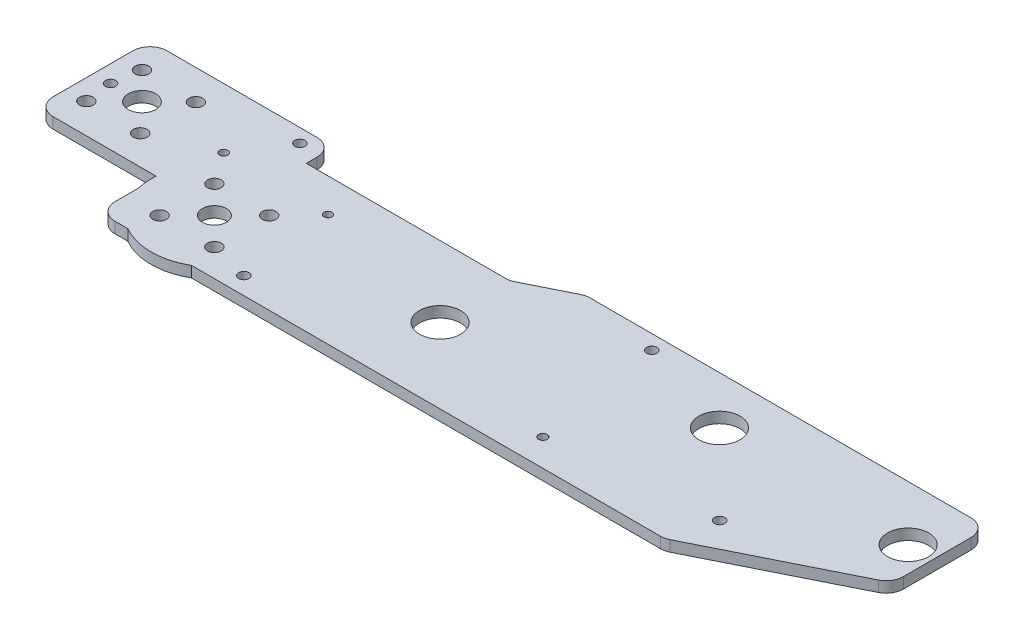
SolidWorks part; units mm, degrees
ref_plane "Front" through (0, 0, 0) normal (0, 0, 1) x (1, 0, 0)
ref_plane "Top" through (0, 0, 0) normal (0, 1, 0) x (1, 0, 0)
ref_plane "Right" through (0, 0, 0) normal (1, 0, 0) x (0, 0, -1)
sketch "Sketch1" plane through (0, 0, 0) normal (0, 1, 0) x (1, 0, 0)
  line L1 (0, 0) -> (210, 0)
  line L2 (0, 0) -> (0, -50)
  line L3 (0, -50) -> (210, -50)
  line L4 (210, 0) -> (210, -50)
  circle A7 centre (3.4895, -16.7877) radius 1.2117
  circle A8 centre (34.3726, -17.194) radius 1.1656
  circle A9 centre (37.5207, -44.9212) radius 1.5
  circle A10 centre (122, -42.0581) radius 1.25
  circle A12 centre (168.9752, -37.4032) radius 1.5173
  circle A13 centre (78.0103, -28.1) radius 3.4
  dimension "D1" = 210
  dimension "D2" = 50
extrude "Boss-Extrude1" add sketch "Sketch1" along normal blind 3.175
sketch "Sketch2" plane through (0, 3.175, 0) normal (0, 1, 0) x (1, 0, 0)
  line L0 (210, 0) -> (0, 0) construction
  line L1 (0, 0) -> (0, -50) construction
  circle A0 centre (10, -26) radius 2
  circle A1 centre (10, -42) radius 2
  circle A2 centre (26, -26) radius 2
  circle A3 centre (26, -42) radius 2
  dimension "D1" = 16
  dimension "D2" = 16
  dimension "D3" = 16
  dimension "D4" = 26
  dimension "D5" = 10
  dimension "D6" = 10
  dimension "D7" = 26
  dimension "D8" = 16
extrude "Cut-Extrude1" cut sketch "Sketch2" against normal blind 10
sketch "Sketch3" plane through (0, 3.175, 0) normal (0, 1, 0) x (1, 0, 0)
  line L0 (210, 0) -> (0, 0) construction
  line L1 (210, 0) -> (0, 0) construction
  circle A0 centre (78.0103, -28.1) radius 6
  circle A1 centre (145.5313, -14) radius 6
  circle A2 centre (18, -34) radius 0.587
  circle A3 centre (26, -26) radius 2 construction
  circle A4 centre (202.6463, -16) radius 6
  dimension "D1" = 28.1
  dimension "D3" = 16
  dimension "D4" = 14
  dimension "D7" = 125.222
  dimension "D2" = 60.2996
  dimension "D5" = 8
  dimension "D6" = 8
  dimension "D8" = 57.15
extrude "Cut-Extrude2" cut sketch "Sketch3" against normal blind 57.15
sketch "Sketch4" [suppressed] plane through (0, 3.175, 0) normal (0, 1, 0) x (1, 0, 0)
  line L0 (3.4895, -16.7877) -> (18, -34)
  line L1 (3.4895, -20.6627) -> (5.9498, -23.5811)
  line L2 (18, -34) -> (34.3726, -17.194)
  line L3 (34.3726, -17.194) -> (75.8499, -28.1)
  line L4 (75.8499, -28.1) -> (37.5207, -44.9212)
  line L5 (7.3432, -17.194) -> (9.8664, -20.303)
  circle A0 centre (18, -34) radius 15.9299
  circle A1 centre (3.4895, -16.7877) radius 3.8751
  circle A2 centre (34.3726, -17.194) radius 3.7227
  circle A3 centre (37.5207, -44.9212) radius 3.8676
  circle A4 centre (75.8499, -28.1) radius 12.797
  circle A5 centre (112.3021, -4.7393) radius 5.1588
  circle A6 centre (118.879, -40.0177) radius 4.9035
  circle A7 centre (140.772, -16) radius 12.6375
  circle A8 centre (168.9752, -37.4032) radius 4.2066
  circle A9 centre (197.922, -16) radius 12.8
sketch "Sketch5" [suppressed] plane through (0, 3.175, 0) normal (0, 1, 0) x (1, 0, 0)
  line L0 (210, 0) -> (0, 0) construction
  line L2 (-0.6266, -16.7877) -> (37.5207, -16.7877)
  line L3 (-0.6266, -16.7877) -> (-0.6266, -44.9212)
  line L4 (-0.6266, -44.9212) -> (37.5207, -44.9212)
  line L5 (37.5207, -16.7877) -> (37.5207, -44.9212)
  line L6 (75.8499, -15.182) -> (37.5207, -15.182)
  line L7 (75.8499, -15.182) -> (75.8499, -44.9212)
  line L8 (75.8499, -44.9212) -> (37.5207, -44.9212)
  line L9 (37.5207, -15.182) -> (37.5207, -44.9212)
  line L10 (112.3021, -4.7393) -> (75.8499, -4.7393)
  line L11 (112.3021, -4.7393) -> (112.3021, -44.9212)
  line L12 (112.3021, -44.9212) -> (75.8499, -44.9212)
  line L13 (75.8499, -4.7393) -> (75.8499, -44.9212)
  line L14 (112.3021, -4.7393) -> (102.3945, -4.7393)
  line L16 (112.3021, -4.7393) -> (112.3021, 0)
  line L17 (112.3021, 0) -> (102.3945, 0)
  line L18 (102.3945, -4.7393) -> (102.3945, 0)
  line L19 (210, -50) -> (210, 0) construction
  line L20 (112.3021, -4.7393) -> (123.1553, -4.7393)
  line L21 (112.3021, -4.7393) -> (112.3021, 0)
  line L22 (112.3021, 0) -> (123.1553, 0)
  line L23 (123.1553, -4.7393) -> (123.1553, 0)
  line L24 (112.3021, -4.7393) -> (140.772, -4.7393)
  line L25 (112.3021, -4.7393) -> (112.3021, -40.0177)
  line L26 (112.3021, -40.0177) -> (140.772, -40.0177)
  line L27 (140.772, -4.7393) -> (140.772, -40.0177)
  line L28 (140.772, -16) -> (168.9752, -16)
  line L29 (140.772, -16) -> (140.772, -40.0177)
  line L30 (140.772, -40.0177) -> (168.9752, -40.0177)
  line L31 (168.9752, -16) -> (168.9752, -40.0177)
  line L32 (168.9752, -4.7393) -> (210, -4.7393)
  line L33 (168.9752, -4.7393) -> (168.9752, -40.0177)
  line L34 (168.9752, -40.0177) -> (210, -40.0177)
  line L35 (210, -4.7393) -> (210, -40.0177)
  line L36 (0, -50) -> (210, -50) construction
  line L37 (160.7629, -40.0177) -> (177.2091, -40.0177)
  line L38 (160.7629, -40.0177) -> (160.7629, -44.9212)
  line L39 (160.7629, -44.9212) -> (177.2091, -44.9212)
  line L40 (177.2091, -40.0177) -> (177.2091, -44.9212)
  line L41 (112.3021, -40.0177) -> (126.3591, -40.0177)
  line L42 (112.3021, -40.0177) -> (112.3021, -47.7828)
  line L43 (112.3021, -47.7828) -> (126.3591, -47.7828)
  line L44 (126.3591, -40.0177) -> (126.3591, -47.7828)
  line L45 (30.5963, -44.9212) -> (44.6115, -44.9212)
  line L46 (30.5963, -44.9212) -> (30.5963, -50)
  line L47 (30.5963, -50) -> (44.6115, -50)
  line L48 (44.6115, -44.9212) -> (44.6115, -50)
  line L50 (-0.6266, -44.9212) -> (30.5963, -44.9212)
  line L51 (-0.6266, -44.9212) -> (-0.6266, -50)
  line L52 (-0.6266, -50) -> (30.5963, -50)
  line L53 (30.5963, -44.9212) -> (30.5963, -50)
  circle A0 centre (3.4895, -16.7877) radius 4.1161
  circle A1 centre (34.3726, -17.194) radius 3.8132
  circle A2 centre (75.8499, -28.1) radius 12.918
  circle A3 centre (112.3021, -4.7393) radius 5.2663
  circle A4 centre (140.772, -16) radius 13.0245
  circle A5 centre (197.922, -16) radius 12.3805
  circle A6 centre (168.9752, -37.4032) radius 4.7643
  circle A7 centre (118.879, -40.0177) radius 5.279
  circle A8 centre (37.5207, -44.9212) radius 4.2049
  line M12 (0, 0) -> (0, -50)
  line M13 (0, -50) -> (210, -50)
  line M14 (210, -50) -> (210, 0)
  line M15 (210, 0) -> (0, 0)
extrude "Cut-Extrude5" [suppressed] cut sketch "Sketch5" against normal blind 11.52 contours A5 L32 L23 L24 A4 L28 L33 M14 M15 | A1 L6 L13 L10 L18 A0 L2 M15 M12 | L8 L48 L34 L40 L39 L38 L30 L26 L44 L43 L42 L12 M13 M14
fillet "Fillet1" [suppressed] radius 5
sketch "Sketch10" plane through (0, 3.175, 0) normal (0, 1, 0) x (1, 0, 0)
  line L0 (210, -27.8594) -> (165.5029, -50)
  line L1 (210, -50) -> (210, 0) construction
  line L2 (0, -50) -> (210, -50) construction
  line L3 (165.5029, -50) -> (210, -50)
  line L4 (210, -50) -> (210, -27.8594)
  line L5 (92.5326, 0) -> (77.6548, -7.4028)
  line L6 (210, 0) -> (0, 0) construction
  line L7 (77.6548, -7.4028) -> (0, -7.4028)
  line L8 (0, 0) -> (0, -50) construction
  line L9 (0, -7.4028) -> (0, 0)
  line L10 (0, 0) -> (92.5326, 0)
extrude "Cut-Extrude7" cut sketch "Sketch10" against normal blind 10
fillet "Fillet3" radius 5 5 edges at (77.6548, 1.5875, 7.4028) (92.5326, 1.5875, 0) (210, 1.5875, 0) (210, 1.5875, 27.8594) (165.5029, 1.5875, 50)
sketch "Sketch11" plane through (0, 3.175, 0) normal (0, 1, 0) x (1, 0, 0)
  circle A0 centre (18, -34) radius 18.5
  circle A1 centre (10, -26) radius 2
  circle A2 centre (10, -42) radius 2
  circle A3 centre (26, -26) radius 2
  circle A4 centre (26, -42) radius 2
extrude "Boss-Extrude4" add sketch "Sketch11" against normal blind 3.175
sketch "Sketch16" plane through (0, 0, 7.4028) normal (0, 0, -1) x (-1, 0, 0)
  line L0 (0, 3.175) -> (-76.4796, 3.175) construction
  line L1 (0, 0) -> (-18.2576, 0)
  line L2 (0, 0) -> (0, 3.175)
  line L3 (0, 3.175) -> (-18.2576, 3.175)
  line L4 (-18.2576, 0) -> (-18.2576, 3.175)
extrude "Boss-Extrude7" add sketch "Sketch16" along normal blind 8.128
sketch "Sketch17" plane through (0, 0, 0) normal (-1, 0, 0) x (0, 0, 1)
  line L0 (-0.7252, 3.175) -> (29.728, 3.175) construction
  line L1 (-0.7252, 0) -> (32.5748, 0)
  line L2 (-0.7252, 0) -> (-0.7252, 3.175)
  line L3 (-0.7252, 3.175) -> (32.5748, 3.175)
  line L4 (32.5748, 0) -> (32.5748, 3.175)
  dimension "D1" = 33.3
extrude "Boss-Extrude8" add sketch "Sketch17" along normal blind 35.56
sketch "Sketch18" plane through (0, 3.175, 0) normal (0, 1, 0) x (1, 0, 0)
  line L0 (-35.56, 0.7252) -> (18.2576, 0.7252) construction
  circle A0 centre (-21.4859, -15.9248) radius 11.315
  circle A1 centre (-29.612, -23.7985) radius 2
  circle A2 centre (-29.3597, -7.7987) radius 2
  circle A3 centre (-13.3598, -8.0511) radius 2
  circle A4 centre (-13.6122, -24.0509) radius 2
  circle A5 centre (-21.4859, -15.9248) radius 4
  point P15 (-21.4859, -15.9248)
  dimension "D1" = 22.63
  dimension "D3" = 4
  dimension "D2" = 16.65
extrude "Cut-Extrude8" cut sketch "Sketch18" against normal blind 9 contours A2 | A1 | A4 | A3
sketch "Sketch19" plane through (0, 3.175, 0) normal (0, 1, 0) x (1, 0, 0)
  circle A0 centre (-21.3597, -15.7987) radius 4
  circle A1 centre (-29.3597, -7.7987) radius 2 construction
  dimension "D1" = 8
  dimension "D2" = 8
extrude "Cut-Extrude9" cut sketch "Sketch19" against normal blind 40
fillet "Fillet4" radius 5 4 edges at (0, 1.5875, 50) (18.2576, 1.5875, -0.7252) (-35.56, 1.5875, -0.7252) (-35.56, 1.5875, 32.5748)
sketch "Sketch20" plane through (0, 3.175, 0) normal (0, 1, 0) x (1, 0, 0)
  circle A0 centre (18, -34) radius 3.5
  circle A1 centre (10, -26) radius 2 construction
  dimension "D1" = 8
  dimension "D2" = 8
extrude "Cut-Extrude10" cut sketch "Sketch20" against normal blind 10
sketch "Sketch21" plane through (0, 3.175, 0) normal (0, 1, 0) x (1, 0, 0)
  line L0 (210, -24.7625) -> (210, -5) construction
  circle A0 centre (116, -4.2372) radius 1.5
  dimension "D1" = 94
extrude "Cut-Extrude11" cut sketch "Sketch21" against normal blind 10
sketch "Sketch22" plane through (0, 3.175, 0) normal (0, 1, 0) x (1, 0, 0)
  line L0 (18.2576, -4.2748) -> (18.2576, -7.4028) construction
  line L1 (-30.56, 0.7252) -> (13.2576, 0.7252) construction
  circle A0 centre (12.2576, -3.2748) radius 1.5
  dimension "D1" = 6
  dimension "D2" = 4
extrude "Cut-Extrude12" cut sketch "Sketch22" against normal blind 10
sketch "Sketch24" plane through (0, 3.175, 0) normal (0, 1, 0) x (1, 0, 0)
  line L0 (-30.56, 0.7252) -> (13.2576, 0.7252) construction
  line L1 (-35.56, -27.5748) -> (-35.56, -4.2748) construction
  circle A0 centre (-30.56, -15.7748) radius 1.5
  dimension "D1" = 16.5
  dimension "D2" = 5
extrude "Cut-Extrude13" cut sketch "Sketch24" against normal blind 10
